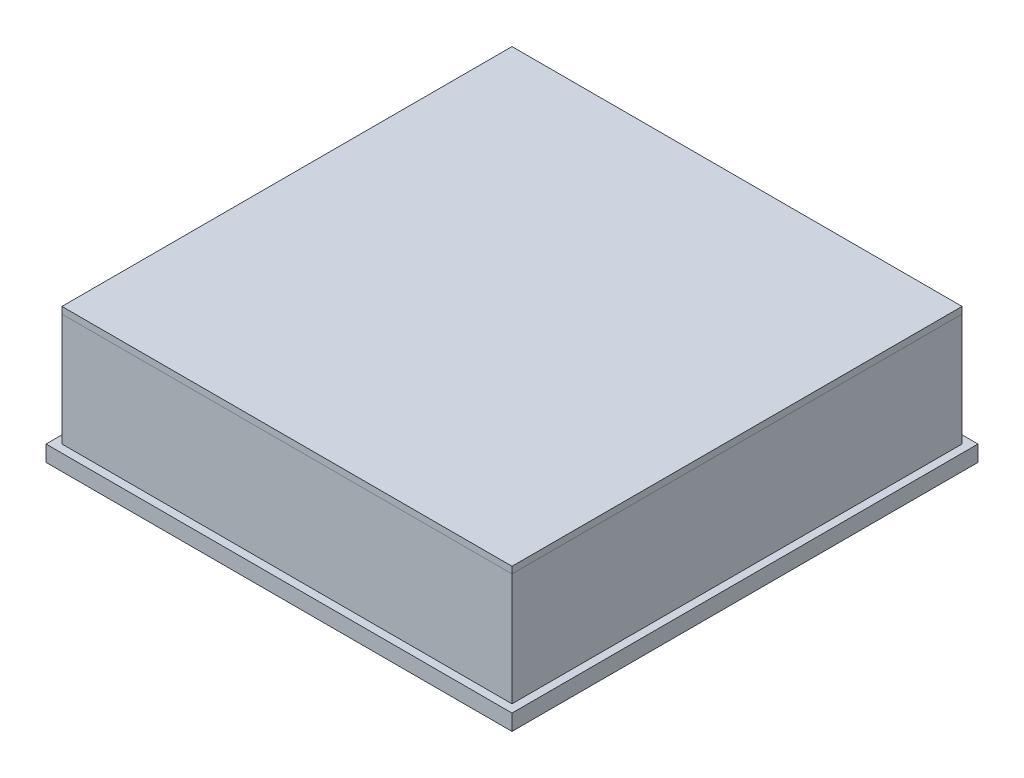
SolidWorks part; units mm, degrees
ref_plane "Front Plane" through (0, 0, 0) normal (0, 0, 1) x (1, 0, 0)
ref_plane "Top Plane" through (0, 0, 0) normal (0, 1, 0) x (1, 0, 0)
ref_plane "Right Plane" through (0, 0, 0) normal (1, 0, 0) x (0, 0, -1)
sketch "Sketch2" plane through (0, 0, 0) normal (0, 1, 0) x (1, 0, 0)
  line L0 (-4304.792, -4304.792) -> (-4304.792, 4304.792)
  line L1 (3999.992, -3999.992) -> (-3999.992, -3999.992)
  line L2 (3999.992, -3999.992) -> (3999.992, 3999.992)
  line L3 (3999.992, 3999.992) -> (-3999.992, 3999.992)
  line L4 (-3999.992, -3999.992) -> (-3999.992, 3999.992)
  line L5 (3999.992, -3999.992) -> (-3999.992, 3999.992) construction
  line L6 (3999.992, 3999.992) -> (-3999.992, -3999.992) construction
  line L7 (4304.792, 4304.792) -> (-4304.792, 4304.792)
  line L8 (4304.792, -4304.792) -> (4304.792, 4304.792)
  line L9 (4304.792, -4304.792) -> (-4304.792, -4304.792)
  point P0 (0, 0)
  dimension "D1" = 7999.984
  dimension "D2" = 7999.984
  dimension "D3" = 304.8
extrude "Boss-Extrude1" add sketch "Sketch2" along normal blind 1999.996
sketch "Sketch3" plane through (0, 0, 0) normal (0, -1, 0) x (1, 0, 0)
  line L0 (-4304.792, -4304.792) -> (-4304.792, 4304.792) construction
  line L1 (-4304.792, -4304.792) -> (-4304.792, 4304.792)
  line L2 (4304.792, -4304.792) -> (-4304.792, -4304.792) construction
  line L3 (4304.792, 4304.792) -> (4304.792, -4304.792) construction
  line L4 (-4304.792, 4304.792) -> (4304.792, 4304.792) construction
  line L5 (4304.792, -4304.792) -> (-4304.792, -4304.792)
  line L6 (4304.792, 4304.792) -> (4304.792, -4304.792)
  line L7 (-4304.792, 4304.792) -> (4304.792, 4304.792)
extrude "Boss-Extrude2" add sketch "Sketch3" along normal blind 152.4
sketch "Sketch4" plane through (0, -152.4, 0) normal (0, -1, 0) x (1, 0, 0)
  line L30 (-4457.192, 4457.192) -> (-4457.192, -4457.192)
  line L31 (-4457.192, -4457.192) -> (4457.192, -4457.192)
  line L32 (4457.192, -4457.192) -> (4457.192, 4457.192)
  line L33 (4457.192, 4457.192) -> (-4457.192, 4457.192)
  line L34 (-4457.192, 4457.192) -> (-4457.192, -4457.192)
  line L35 (-4457.192, -4457.192) -> (4457.192, -4457.192)
  line L36 (4457.192, -4457.192) -> (4457.192, 4457.192)
  line L37 (4457.192, 4457.192) -> (-4457.192, 4457.192)
  line L43 (3847.592, 3847.592) -> (-3847.592, 3847.592)
  line L44 (-3847.592, 3847.592) -> (-3847.592, -3847.592)
  line L45 (-3847.592, -3847.592) -> (3847.592, -3847.592)
  line L46 (3847.592, -3847.592) -> (3847.592, 3847.592)
  line L47 (3847.592, 3847.592) -> (-3847.592, 3847.592)
  line L48 (-3847.592, 3847.592) -> (-3847.592, -3847.592)
  line L49 (-3847.592, -3847.592) -> (3847.592, -3847.592)
  line L50 (3847.592, -3847.592) -> (3847.592, 3847.592)
  dimension "D1" = 152.4
  dimension "D2" = 152.4
extrude "Boss-Extrude3" add sketch "Sketch4" along normal blind 304.8
sketch "Sketch6" plane through (0, 0, 0) normal (0, 1, 0) x (1, 0, 0)
  line L0 (0, 0) -> (-3999.992, 3999.992) construction
  line L6 (-3999.992, 1656.8509) -> (-1656.8509, 1656.8509) construction
  line L7 (-3999.992, 3999.992) -> (-3999.992, -3999.992) construction
  line L19 (-1656.8509, 1656.8509) -> (-1656.8509, 3999.992) construction
  line L20 (3999.992, 3999.992) -> (-3999.992, 3999.992) construction
  line L22 (-1656.8509, 1656.8509) -> (0, 0) construction
  line L24 (1809.2509, 1504.4509) -> (1809.2509, 1809.2509)
  line L25 (-1504.4509, 1809.2509) -> (-1809.2509, 1809.2509)
  line L29 (-1504.4509, 1809.2509) -> (-1504.4509, 1504.4509)
  line L30 (-1504.4509, 1504.4509) -> (-1809.2509, 1504.4509)
  line L31 (-1809.2509, 1809.2509) -> (-1809.2509, 1504.4509)
  line L32 (-1504.4509, 1809.2509) -> (-1809.2509, 1504.4509) construction
  line L33 (-1504.4509, 1504.4509) -> (-1809.2509, 1809.2509) construction
  line L34 (1809.2509, 1809.2509) -> (1504.4509, 1809.2509)
  line L35 (1504.4509, 1504.4509) -> (1504.4509, 1809.2509)
  line L36 (1809.2509, 1504.4509) -> (1504.4509, 1504.4509)
  line L37 (1504.4509, -1809.2509) -> (1809.2509, -1809.2509)
  line L38 (1809.2509, -1809.2509) -> (1809.2509, -1504.4509)
  line L39 (1504.4509, -1504.4509) -> (1809.2509, -1504.4509)
  line L40 (1504.4509, -1809.2509) -> (1504.4509, -1504.4509)
  line L41 (-1809.2509, -1504.4509) -> (-1809.2509, -1809.2509)
  line L42 (-1809.2509, -1809.2509) -> (-1504.4509, -1809.2509)
  line L43 (-1504.4509, -1504.4509) -> (-1504.4509, -1809.2509)
  line L44 (-1809.2509, -1504.4509) -> (-1504.4509, -1504.4509)
  point P30 (0, 0)
  dimension "D1" = 304.8
extrude "Boss-Extrude5" add sketch "Sketch6" along normal up to surface (1999.996 mm away) contours L25 L31 L30 L29 | L36 L24 L34 L35 | L40 L37 L38 L39 | L44 L41 L42 L43 region at (1656.8509, 0, -1656.8509) region at (-1656.8509, 0, -1656.8509) region at (1656.8509, 0, 1656.8509) region at (-1656.8509, 0, 1656.8509) up to face at (0, 1999.996, 0)
sketch "Sketch7" plane through (0, 1999.996, 0) normal (0, 1, 0) x (1, 0, 0)
  line L1 (4304.792, -4304.792) -> (-4304.792, -4304.792)
  line L2 (4304.792, -4304.792) -> (4304.792, 4304.792)
  line L3 (4304.792, 4304.792) -> (-4304.792, 4304.792)
  line L4 (-4304.792, -4304.792) -> (-4304.792, 4304.792)
  line L5 (4304.792, -4304.792) -> (-4304.792, 4304.792) construction
  line L6 (4304.792, 4304.792) -> (-4304.792, -4304.792) construction
  point P0 (0, 0)
extrude "Boss-Extrude6" add sketch "Sketch7" along normal blind 127 separate body
sketch "Sketch8" plane through (0, 0, -1504.4509) normal (0, 0, 1) x (1, 0, 0)
  line L0 (-3999.992, 1999.996) -> (-3999.992, 0) construction
  line L1 (3999.992, 1999.996) -> (-3999.992, 1999.996)
  line L2 (3999.992, 1999.996) -> (3999.992, 1753.1524)
  line L3 (3999.992, 1753.1524) -> (-3999.992, 1753.1524)
  line L4 (-3999.992, 1999.996) -> (-3999.992, 1753.1524)
  line L5 (3999.992, 1999.996) -> (-3999.992, 1753.1524) construction
  line L6 (3999.992, 1753.1524) -> (-3999.992, 1999.996) construction
  line L7 (3999.992, 1999.996) -> (-3999.992, 1999.996) construction
  line L8 (3999.992, 1999.996) -> (-3999.992, 1999.996)
  point P0 (0, 1876.5742)
ref_axis "Axis1" through (0, 0, 0) along (0, 1, 0)
sketch "Right Plane Rebar" plane through (0, 0, 0) normal (1, 0, 0) x (0, 0, -1)
  line L0 (4234.942, 2063.496) -> (4234.942, -393.7)
  line L1 (-4457.192, -457.2) -> (4457.192, -457.2) construction
  line L2 (4069.842, 2044.446) -> (4069.842, 50.8)
  line L3 (4222.242, 1314.196) -> (4222.242, 1923.796)
  line L4 (-4304.792, 1999.996) -> (-4304.792, -152.4)
  line L5 (-4304.792, -152.4) -> (4304.792, -152.4)
  line L6 (4304.792, -152.4) -> (4304.792, 1999.996)
  line L7 (4304.792, 1999.996) -> (-4304.792, 1999.996)
  line L8 (-4304.792, 1999.996) -> (-4304.792, -152.4)
  line L9 (-4304.792, -152.4) -> (4304.792, -152.4)
  line L10 (4304.792, -152.4) -> (4304.792, 1999.996)
  line L12 (4095.242, 2050.796) -> (3485.642, 2050.796)
  line L13 (4095.242, 2063.496) -> (-4095.242, 2063.496)
  line L14 (0, 1421.3078) -> (0, -1421.3078) construction
  line L15 (3955.542, -88.9) -> (-3955.542, -88.9)
  line L16 (3999.992, 1999.996) -> (-3999.992, 1999.996)
  line L17 (3999.992, 1999.996) -> (-3999.992, 1999.996)
  line L18 (-4304.792, 2126.996) -> (4304.792, 2126.996) construction
  line L19 (3999.992, 0) -> (3999.992, 1999.996)
  line L20 (-3999.992, 0) -> (3999.992, 0)
  line L21 (-3999.992, 1999.996) -> (-3999.992, 0)
  line L27 (3999.992, 0) -> (3999.992, 1999.996)
  line L28 (-3999.992, 0) -> (3999.992, 0)
  line L29 (-3999.992, 1999.996) -> (-3999.992, 0)
  line L32 (4082.542, 660.4) -> (4082.542, 50.8)
  line L33 (3955.542, -76.2) -> (3345.942, -76.2)
  line L38 (4304.792, 1999.996) -> (-4304.792, 1999.996)
  arc A0 (4222.242, 1923.796) -> (4095.242, 2050.796) centre (4095.242, 1923.796) ccw
  arc A1 (3955.542, -76.2) -> (4082.542, 50.8) centre (3955.542, 50.8) ccw
  point P23 (4222.242, 2050.796)
  point P30 (0, 2063.496)
  point P41 (0, -88.9)
  dimension "D12" = 127
  dimension "D19" = 127
  dimension "D5" = 69.85
  dimension "Vertical Rebar Outer" = 2457.196
  dimension "D4" = 63.5
  dimension "D8" = 69.85
  dimension "D11" = 12.7
  dimension "D10" = 6.35
  dimension "D13" = 609.6
  dimension "D14" = 609.6
  dimension "D15" = 12.7
  dimension "D16" = 63.5
  dimension "D17" = 12.7
  dimension "D18" = 12.7
  dimension "D7" = 609.6
  dimension "D20" = 609.6
  dimension "Vertical Rebar Inner" = 1993.646
  dimension "Lid Rebar Length" = 8190.484
  dimension "Base Rebar Length" = 7911.084
  dimension "D3" = 63.5
  dimension "D6" = 63.5
sketch "Front Plane Rebar" plane through (0, 0, 0) normal (0, 0, 1) x (1, 0, 0)
  line L0 (4247.642, 2063.496) -> (4247.642, -393.7)
  line L1 (3999.992, 1999.996) -> (3999.992, 0) construction
  line L2 (4057.142, 2031.746) -> (4057.142, 63.5)
  line L3 (4234.942, 1301.496) -> (4234.942, 1911.096)
  line L4 (-4304.792, 2126.996) -> (4304.792, 2126.996) construction
  line L5 (4457.192, -457.2) -> (-4457.192, -457.2) construction
  line L6 (4457.192, -152.4) -> (-4457.192, -152.4) construction
  line L7 (4304.792, 2126.996) -> (-4304.792, 2126.996) construction
  line L8 (-4304.792, 1999.996) -> (-4304.792, -152.4)
  line L9 (-4304.792, -152.4) -> (4304.792, -152.4)
  line L10 (4304.792, -152.4) -> (4304.792, 1999.996)
  line L12 (4107.942, 2038.096) -> (3498.342, 2038.096)
  line L13 (4107.942, 2050.796) -> (-4107.942, 2050.796)
  line L15 (3942.842, -76.2) -> (-3942.842, -76.2)
  line L17 (3999.992, 1999.996) -> (-3999.992, 1999.996)
  line L19 (-3999.992, 0) -> (3999.992, 0)
  line L20 (3999.992, 0) -> (3999.992, 1999.996)
  line L21 (3999.992, 1999.996) -> (-3999.992, 1999.996)
  line L22 (-3999.992, 1999.996) -> (-3999.992, 0)
  line L23 (-3999.992, 0) -> (3999.992, 0)
  line L27 (3999.992, 0) -> (3999.992, 1999.996)
  line L28 (-3999.992, 0) -> (3999.992, 0)
  line L29 (-3999.992, 1999.996) -> (-3999.992, 0)
  line L32 (4069.842, 673.1) -> (4069.842, 63.5)
  line L33 (3942.842, -63.5) -> (3333.242, -63.5)
  line L34 (3999.992, 0) -> (3999.992, 1999.996)
  line L35 (3999.992, 1999.996) -> (-3999.992, 1999.996)
  line L36 (-3999.992, 1999.996) -> (-3999.992, 0)
  line L37 (4304.792, -152.4) -> (4304.792, 1999.996)
  line L38 (4304.792, 1999.996) -> (-4304.792, 1999.996)
  line L39 (-4304.792, -152.4) -> (4304.792, -152.4)
  line L40 (-4304.792, 1999.996) -> (-4304.792, -152.4)
  line L41 (4304.792, 1999.996) -> (-4304.792, 1999.996)
  line L42 (4304.792, -152.4) -> (4304.792, 1999.996)
  line L43 (-4304.792, -152.4) -> (4304.792, -152.4)
  line L44 (-4304.792, 1999.996) -> (-4304.792, -152.4)
  line L45 (4304.792, 1999.996) -> (-4304.792, 1999.996)
  arc A0 (4234.942, 1911.096) -> (4107.942, 2038.096) centre (4107.942, 1911.096) ccw
  arc A1 (3942.842, -63.5) -> (4069.842, 63.5) centre (3942.842, 63.5) ccw
  point P23 (4234.942, 2038.096)
  point P30 (0, 2050.796)
  point P41 (0, -76.2)
  dimension "D12" = 127
  dimension "D19" = 127
  dimension "Vertical Rebar Outer" = 2457.196
  dimension "D4" = 63.5
  dimension "D11" = 12.7
  dimension "D10" = 6.35
  dimension "D13" = 609.6
  dimension "D14" = 609.6
  dimension "D15" = 12.7
  dimension "D17" = 12.7
  dimension "D18" = 12.7
  dimension "D7" = 609.6
  dimension "D20" = 609.6
  dimension "D5" = 57.15
  dimension "D8" = 57.15
  dimension "D16" = 76.2
  dimension "Vertical Rebar Inner" = 1968.246
  dimension "Lid Rebar Length" = 8215.884
  dimension "Base Rebar Length" = 7885.684
  dimension "D3" = 76.2
  dimension "D21" = 63.5
sketch "Sketch9" plane through (0, -152.4, 0) normal (0, 1, 0) x (1, 0, 0)
  line L0 (-4260.342, 4393.692) -> (-4260.342, -4393.692)
  line L1 (-4457.192, -4457.192) -> (-4457.192, 4457.192) construction
  line L2 (-4457.192, -4457.192) -> (-4457.192, 4457.192)
  line L3 (-3847.592, -3847.592) -> (-3847.592, 3847.592) construction
  line L4 (-3847.592, -3847.592) -> (-3847.592, 3847.592)
  line L5 (-4457.192, 4457.192) -> (4457.192, 4457.192) construction
  line L6 (4457.192, -4457.192) -> (-4457.192, -4457.192) construction
  line L7 (-4044.442, 4152.392) -> (-4044.442, -4152.392)
  line L8 (4393.692, 4260.342) -> (-4393.692, 4260.342)
  line L9 (4152.392, 4044.442) -> (-4152.392, 4044.442)
  line L10 (4260.342, -4393.692) -> (4260.342, 4393.692)
  line L11 (4044.442, -4152.392) -> (4044.442, 4152.392)
  line L12 (-4393.692, -4260.342) -> (4393.692, -4260.342)
  line L13 (-4152.392, -4044.442) -> (4152.392, -4044.442)
  point P27 (0, 0)
  dimension "D3" = 63.5
  dimension "D1" = 196.85
  dimension "D2" = 63.5
  dimension "D4" = 196.85
  dimension "D5" = 304.8
  dimension "D6" = 304.8
  dimension "D7" = 8787.384
  dimension "D8" = 8304.784
  dimension "D9" = 4
sketch "Sketch11" plane through (0, 0, -1504.4509) normal (0, 0, 1) x (1, 0, 0)
  line L0 (-1745.7509, 2063.496) -> (-1745.7509, -88.9)
  line L1 (-1745.7509, 2063.496) -> (-1745.7509, 1930.146)
  line L2 (-4304.792, 2126.996) -> (4304.792, 2126.996) construction
  line L4 (4457.192, -152.4) -> (-4457.192, -152.4) construction
  line L5 (-1745.7509, -88.9) -> (-1745.7509, 44.45)
  line L6 (-1504.4509, 0) -> (-1504.4509, 1999.996)
  line L7 (-1504.4509, 1999.996) -> (-1809.2509, 1999.996)
  line L8 (-1809.2509, 1999.996) -> (-1809.2509, 0)
  line L9 (-1809.2509, 0) -> (-1504.4509, 0)
  line L10 (-1504.4509, 0) -> (-1504.4509, 1999.996)
  line L11 (-1504.4509, 1999.996) -> (-1809.2509, 1999.996)
  line L12 (-1809.2509, 1999.996) -> (-1809.2509, 0)
  line L13 (-1809.2509, 0) -> (-1504.4509, 0)
  dimension "D4" = 63.5
  dimension "D2" = 63.5
  dimension "D3" = 133.35
  dimension "D5" = 63.5
  dimension "D6" = 133.35
  dimension "D7" = 1885.696
sketch "Sketch13" plane through (0, 2126.996, 0) normal (0, 1, 0) x (1, 0, 0)
  line L0 (-4222.242, 4253.992) -> (-4222.242, -4253.992)
  line L1 (-4304.792, 4304.792) -> (-4304.792, -4304.792) construction
  line L2 (-4304.792, 4304.792) -> (4304.792, 4304.792) construction
  line L3 (4304.792, -4304.792) -> (-4304.792, -4304.792) construction
  dimension "D1" = 82.55
  dimension "D2" = 50.8
  dimension "D3" = 50.8
  dimension "D4" = 8507.984
ref_plane "Plane1" through (-4304.792, 1999.996, -4304.792) normal (0, -1, 0) x (-1, 0, 0)
equation "\"Rebar Diameter\"=0.5"
equation "\"Min Coverage\"=2.5"
equation "\"D5@Right Plane Rebar\" = \"Rebar Diameter\" / 2 + \"Min Coverage\""
equation "\"D4@Right Plane Rebar\" = \"Min Coverage\""
equation "\"D8@Right Plane Rebar\" = \"Min Coverage\" + \"Rebar Diameter\" / 2"
equation "\"Contact Length\"= 24"
equation "\"D11@Right Plane Rebar\" = \"Rebar Diameter\""
equation "\"Rebar Bend Radius\"= 5"
equation "\"D12@Right Plane Rebar\" = \"Rebar Bend Radius\""
equation "\"D10@Right Plane Rebar\" = \"Rebar Diameter\" / 2"
equation "\"D13@Right Plane Rebar\" = \"Contact Length\""
equation "\"D14@Right Plane Rebar\" = \"Contact Length\""
equation "\"D15@Right Plane Rebar\" = \"Rebar Diameter\""
equation "\"D16@Right Plane Rebar\" = \"Min Coverage\""
equation "\"D17@Right Plane Rebar\" = \"Rebar Diameter\""
equation "\"D18@Right Plane Rebar\" = \"Rebar Diameter\""
equation "\"D19@Right Plane Rebar\" = \"Rebar Bend Radius\""
equation "\"D7@Right Plane Rebar\" = \"Contact Length\""
equation "\"D20@Right Plane Rebar\" = \"Contact Length\""
equation "\"D3@Right Plane Rebar\" = \"Min Coverage\""
equation "\"D6@Right Plane Rebar\" = \"Min Coverage\""
equation "\"D3@Front Plane Rebar\" = \"Rebar Diameter\" + \"Min Coverage\""
equation "\"D4@Front Plane Rebar\" = \"Min Coverage\""
equation "\"D16@Front Plane Rebar\" = \"Min Coverage\" + \"Rebar Diameter\""
equation "\"D21@Front Plane Rebar\" = \"Min Coverage\""
equation "\"D1@Sketch9\"=7.75"
equation "\"D2@Sketch9\"=\"Min Coverage\""
equation "\"D3@Sketch9\"=\"Min Coverage\""
equation "\"D4@Sketch9\"=7.75"
equation "\"D4@Sketch11\"=\"Min Coverage\""
equation "\"D2@Sketch11\"=\"Min Coverage\""
